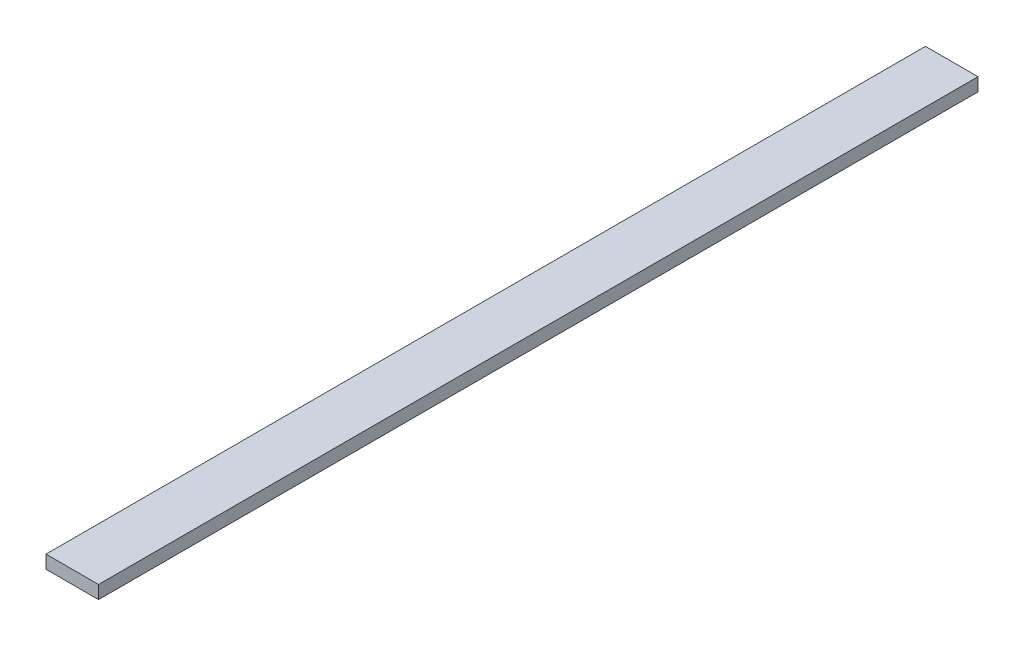
SolidWorks part; units mm, degrees
material "Acrylic (Medium-high impact)"
ref_plane "Front Plane" through (0, 0, 0) normal (0, 0, 1) x (1, 0, 0)
ref_plane "Top Plane" through (0, 0, 0) normal (0, 1, 0) x (1, 0, 0)
ref_plane "Right Plane" through (0, 0, 0) normal (1, 0, 0) x (0, 0, -1)
sketch "Sketch1" plane through (0, 0, 0) normal (0, 0, 1) x (1, 0, 0)
  line L1 (0, 0) -> (19.05, 0)
  line L2 (0, 0) -> (0, 4.7625)
  line L3 (0, 4.7625) -> (19.05, 4.7625)
  line L4 (19.05, 0) -> (19.05, 4.7625)
  dimension "D1" = 19.05
  dimension "D2" = 4.7625
extrude "Boss-Extrude1" add sketch "Sketch1" along normal blind 343.95
sketch "Sketch2" plane through (19.05, 0, 0) normal (1, 0, 0) x (0, 0, -1)
  line L0 (-343.95, 0) -> (0, 0) construction
  line L1 (0, 4.7625) -> (-25.1341, 4.7625)
  line L2 (0, 4.7625) -> (0, 0)
  line L3 (0, 0) -> (-25.1341, 0)
  line L4 (-25.1341, 4.7625) -> (-25.1341, 0)
extrude "Cut-Extrude1" cut sketch "Sketch2" against normal through all
